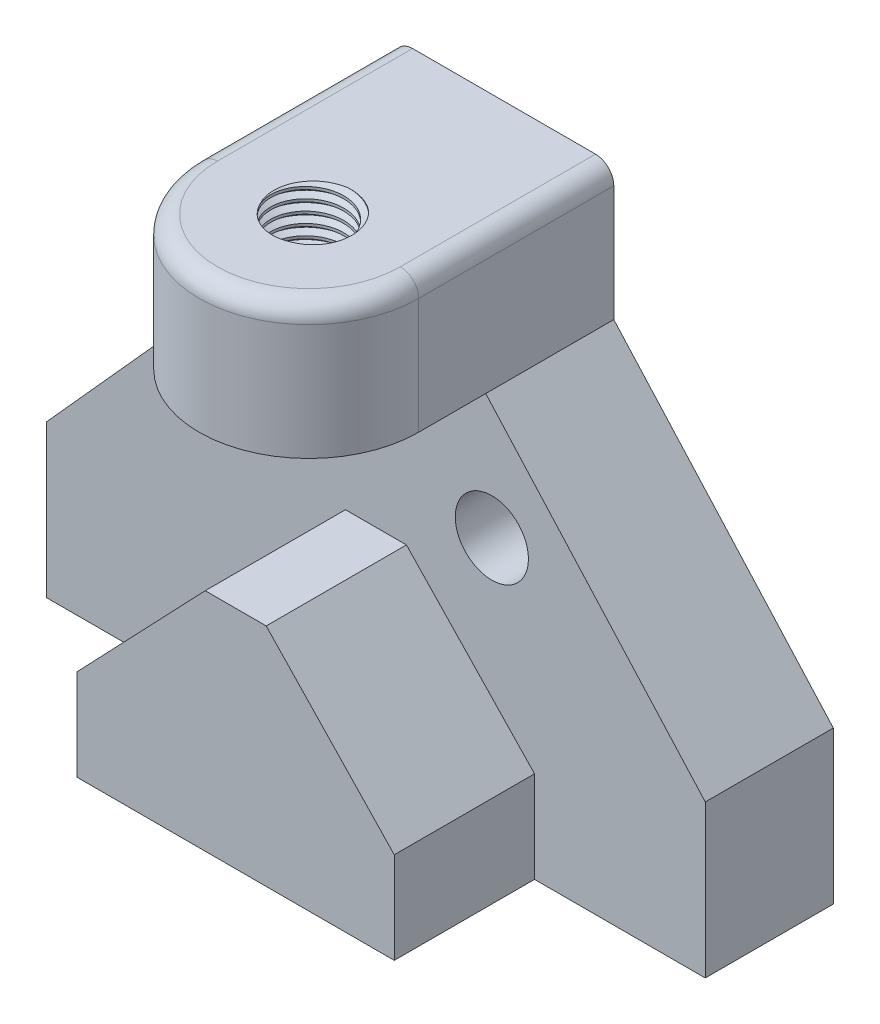
SolidWorks part; units mm, degrees
ref_plane "정면" through (0, 0, 0) normal (0, 0, 1) x (1, 0, 0)
ref_plane "윗면" through (0, 0, 0) normal (0, 1, 0) x (1, 0, 0)
ref_plane "우측면" through (0, 0, 0) normal (1, 0, 0) x (0, 0, -1)
sketch "스케치3" plane through (0, 0, 0) normal (0, 0, 1) x (1, 0, 0)
  line L7 (54, 25) -> (18, 65)
  line L8 (18, 65) -> (-18, 65)
  line L9 (-18, 65) -> (-54, 25)
  line L10 (-54, 25) -> (-54, 0)
  line L11 (54, 25) -> (54, 0)
  line L12 (-54, 0) -> (54, 0)
  point P1 (0, 0)
  point P3 (-54, 49.0251)
  point P4 (0, 0)
  dimension "D1" = 54
  dimension "D2" = 108
  dimension "D3" = 65
  dimension "D7" = 25
  dimension "D10" = 36
  dimension "D11" = 18
extrude "보스-돌출1" add sketch "스케치3" along normal blind 21
sketch "스케치4" plane through (0, 0, 21) normal (0, 0, 1) x (1, 0, 0)
  line L0 (-26, 0) -> (26, 0)
  line L1 (-54, 0) -> (54, 0) construction
  line L2 (26, 0) -> (26, 15)
  line L3 (26, 15) -> (5, 37)
  line L4 (5, 37) -> (-5, 37)
  line L5 (-5, 37) -> (-26, 15)
  line L6 (-26, 15) -> (-26, 0)
  dimension "D1" = 52
  dimension "D2" = 15
  dimension "D3" = 15
  dimension "D4" = 5
  dimension "D5" = 5
  dimension "D6" = 37
extrude "보스-돌출2" add sketch "스케치4" along normal blind 23
sketch "스케치5" plane through (0, 65, 0) normal (0, 1, 0) x (1, 0, 0)
  line L1 (-18, 0) -> (18, 0)
  line L2 (-18, 0) -> (-18, -32)
  line L4 (18, 0) -> (18, -32)
  line L6 (-18, -21) -> (-18, 0) construction
  arc A0 (-18, -32) -> (18, -32) centre (0, -32) ccw
  dimension "D1" = 32
extrude "보스-돌출3" add sketch "스케치5" along normal blind 22
sketch "스케치7" plane through (0, 87, 0) normal (0, 1, 0) x (1, 0, 0)
  circle A0 centre (0, -32) radius 6
  arc A1 (-18, -32) -> (18, -32) centre (0, -32) ccw construction
  dimension "D1" = 12
extrude "컷-돌출1" cut sketch "스케치7" against normal up to next
sketch "스케치8" plane through (0, 0, 21) normal (0, 0, 1) x (1, 0, 0)
  line L0 (0, -4.8026) -> (0, 76.0111) construction
  circle A0 centre (-19, 45) radius 6
  circle A1 centre (19, 45) radius 6
  dimension "D1" = 12
  dimension "D2" = 19
  dimension "D3" = 45
extrude "컷-돌출2" cut sketch "스케치8" against normal through all
thread "나사산2" pitch 1.75 method cut profile "나사산 프로파일2" start angle 0, offset 0, length 0, pitch 1.75, diameter 12
ref_plane "평면2" through (6, 65, 32) normal (0, 0, 1) x (1, 0, 0)
sketch "나사산 프로파일2" plane through (6, 65, 32) normal (0, 0, 1) x (1, 0, 0)
  line L0 (0, 0) -> (0, 1.75) construction
  line L1 (0, 0) -> (0.9472, 0.5469)
  line L2 (0.9472, 0.5469) -> (0.9472, 0.7656)
  line L3 (0.9472, 0.7656) -> (0, 1.3125)
  line L4 (0.9472, 0.6562) -> (0, 0.6562) construction
  line L11 (0, 0) -> (0, 1.3125)
  point P2 (0, 0)
  dimension "Pitch" = 1.75
  dimension "Profile_Angle" = 60
  dimension "Profile_Land" = 0.2188
  dimension "Profile_Height" = 0.9472
fillet "필렛1" radius 3 3 edges at (-18, 87, 16) (18, 87, 16) (0, 87, 50)
chamfer "모따기1" distance 0.2 angle 45 2 edges at (-13, 45, 0) (13, 45, 0)
